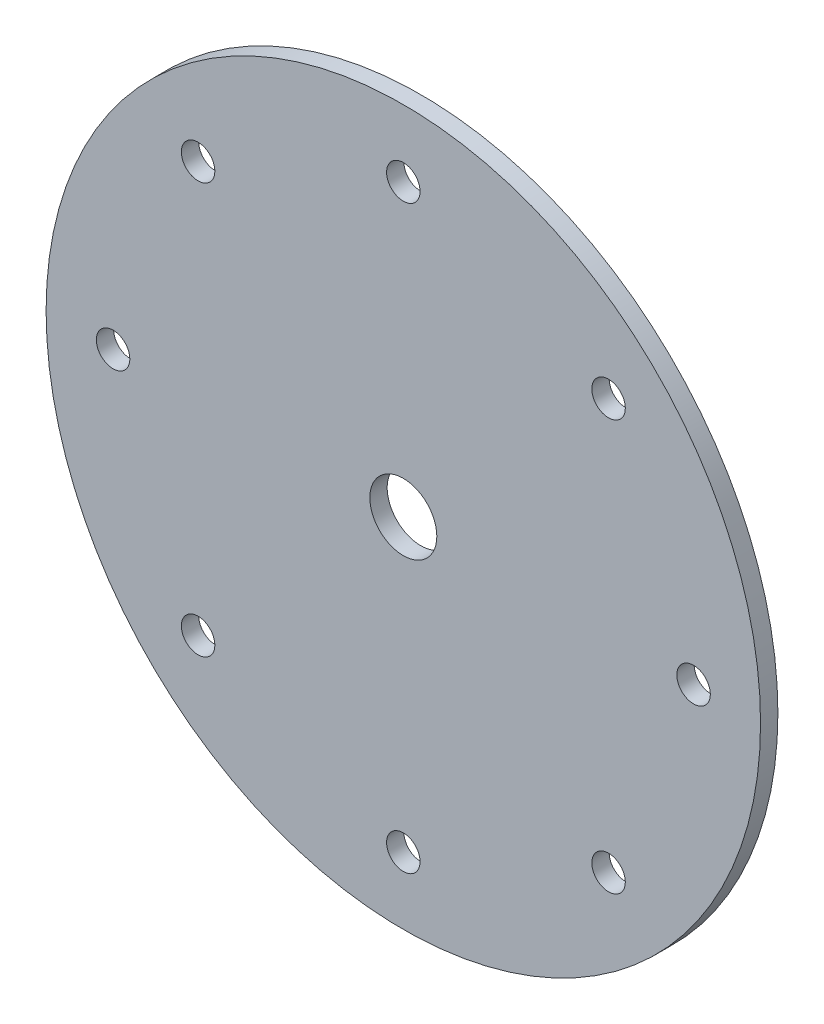
SolidWorks part; units mm, degrees
material "Plain Carbon Steel"
ref_plane "Front Plane" through (0, 0, 0) normal (0, 0, 1) x (1, 0, 0)
ref_plane "Top Plane" through (0, 0, 0) normal (0, 1, 0) x (1, 0, 0)
ref_plane "Right Plane" through (0, 0, 0) normal (1, 0, 0) x (0, 0, -1)
sketch "Sketch1" plane through (0, 0, 0) normal (0, 0, 1) x (1, 0, 0)
  line L0 (0, 101.6) -> (0, -101.6) construction
  line L1 (-101.6, 0) -> (101.6, 0) construction
  line L2 (-58.3717, 58.3717) -> (58.3717, -58.3717) construction
  line L3 (-58.3717, -58.3717) -> (58.3717, 58.3717) construction
  circle A0 centre (0, 0) radius 101.6
  circle A1 centre (0, 0) radius 9.525
  circle A2 centre (0, 82.55) radius 4.7625
  circle A6 centre (58.3717, 58.3717) radius 4.7625
  circle A7 centre (82.55, 0) radius 4.7625
  circle A8 centre (58.3717, -58.3717) radius 4.7625
  circle A9 centre (0, -82.55) radius 4.7625
  circle A10 centre (-58.3717, -58.3717) radius 4.7625
  circle A11 centre (-82.55, 0) radius 4.7625
  circle A12 centre (-58.3717, 58.3717) radius 4.7625
  dimension "D1" = 203.2
  dimension "D2" = 19.05
  dimension "D3" = 9.525
  dimension "D6" = 19.05
  dimension "D4" = 19.05
  dimension "D5" = 8
extrude "Rotor Disc" add sketch "Sketch1" along normal blind 4.9352 contours A0 A12 A11 A10 A8 A7 A6 A1 A2 region at (-98.7263, 0, 0)
